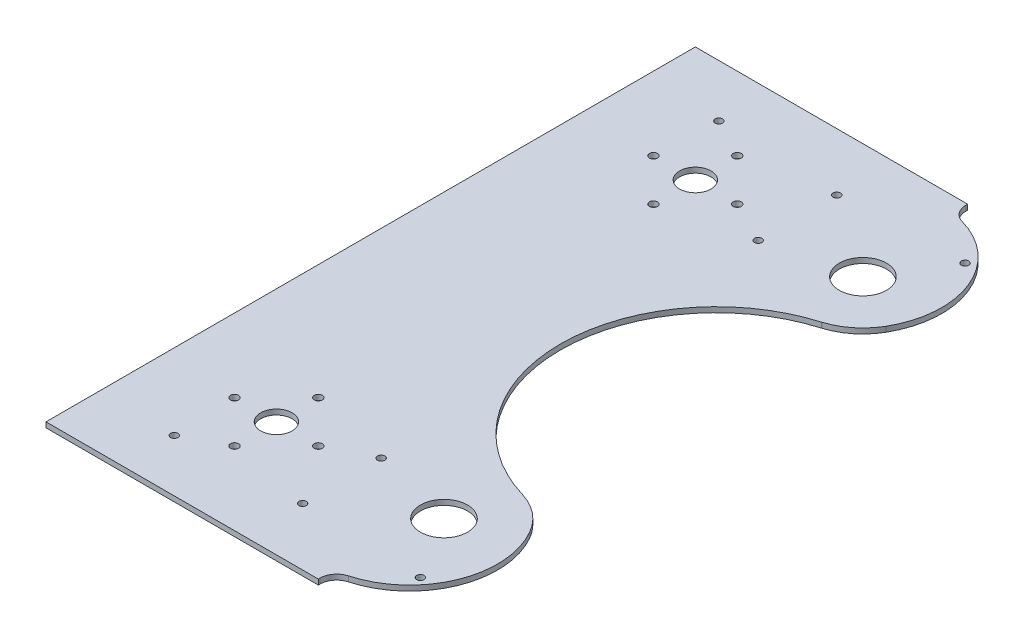
SolidWorks part; units mm, degrees
material "6061-T6 (SS)"
ref_plane "Front Plane" through (0, 0, 0) normal (0, 0, 1) x (1, 0, 0)
ref_plane "Top Plane" through (0, 0, 0) normal (0, 1, 0) x (1, 0, 0)
ref_plane "Right Plane" through (0, 0, 0) normal (1, 0, 0) x (0, 0, -1)
sketch "Sketch1" plane through (0, 0, 0) normal (0, 1, 0) x (1, 0, 0)
  line L1 (82.55, -196.85) -> (-82.55, -196.85)
  line L2 (82.55, -196.85) -> (82.55, 196.85)
  line L3 (82.55, 196.85) -> (-82.55, 196.85)
  line L4 (-82.55, -196.85) -> (-82.55, 196.85)
  line L5 (82.55, -196.85) -> (-82.55, 196.85) construction
  line L6 (82.55, 196.85) -> (-82.55, -196.85) construction
  point P0 (0, 0)
  dimension "D1" = 165.1
  dimension "D2" = 393.7
extrude "Boss-Extrude1" add sketch "Sketch1" along normal blind 3.175
sketch "Sketch3" plane through (0, 3.175, 0) normal (0, 1, 0) x (1, 0, 0)
  arc A0 (-3.175, -127) -> (-22.225, -127) centre (-12.7, -127) ccw construction
  arc A1 (-22.225, -127) -> (-3.175, -127) centre (-12.7, -127) ccw construction
  arc A2 (-3.175, -127) -> (-22.225, -127) centre (-12.7, -127) ccw
  arc A3 (-22.225, -127) -> (-3.175, -127) centre (-12.7, -127) ccw
  arc A4 (-3.175, 127) -> (-22.225, 127) centre (-12.7, 127) ccw construction
  arc A5 (-22.225, 127) -> (-3.175, 127) centre (-12.7, 127) ccw construction
  arc A6 (-3.175, 127) -> (-22.225, 127) centre (-12.7, 127) ccw
  arc A7 (-22.225, 127) -> (-3.175, 127) centre (-12.7, 127) ccw
extrude "Cut-Extrude2" cut sketch "Sketch3" against normal through all
hole_wizard "#10 (0.1935) Diameter Hole1" positions "Sketch4" profile "Sketch5" hole size "#10" standard "ANSI Inch" end condition through all
sketch "Sketch4" plane through (0, 3.175, 0) normal (0, 1, 0) x (1, 0, 0)
  arc A0 (-10.6807, -101.6) -> (-14.7193, -101.6) centre (-12.7, -101.6) ccw construction
  arc A1 (-14.7193, -101.6) -> (-10.6807, -101.6) centre (-12.7, -101.6) ccw construction
  arc A2 (-36.0807, -127) -> (-40.1193, -127) centre (-38.1, -127) ccw construction
  arc A3 (-40.1193, -127) -> (-36.0807, -127) centre (-38.1, -127) ccw construction
  arc A4 (-10.6807, -152.4) -> (-14.7193, -152.4) centre (-12.7, -152.4) ccw construction
  arc A5 (-14.7193, -152.4) -> (-10.6807, -152.4) centre (-12.7, -152.4) ccw construction
  arc A6 (14.7193, -127) -> (10.6807, -127) centre (12.7, -127) ccw construction
  arc A7 (10.6807, -127) -> (14.7193, -127) centre (12.7, -127) ccw construction
  arc A8 (-10.6807, -101.6) -> (-14.7193, -101.6) centre (-12.7, -101.6) ccw construction
  arc A9 (-14.7193, -101.6) -> (-10.6807, -101.6) centre (-12.7, -101.6) ccw construction
  arc A10 (-36.0807, -127) -> (-40.1193, -127) centre (-38.1, -127) ccw construction
  arc A11 (-40.1193, -127) -> (-36.0807, -127) centre (-38.1, -127) ccw construction
  arc A12 (-10.6807, -152.4) -> (-14.7193, -152.4) centre (-12.7, -152.4) ccw construction
  arc A13 (-14.7193, -152.4) -> (-10.6807, -152.4) centre (-12.7, -152.4) ccw construction
  arc A14 (14.7193, -127) -> (10.6807, -127) centre (12.7, -127) ccw construction
  arc A15 (10.6807, -127) -> (14.7193, -127) centre (12.7, -127) ccw construction
  arc A16 (14.7193, 127) -> (10.6807, 127) centre (12.7, 127) ccw construction
  arc A17 (10.6807, 127) -> (14.7193, 127) centre (12.7, 127) ccw construction
  arc A18 (-10.6807, 152.4) -> (-14.7193, 152.4) centre (-12.7, 152.4) ccw construction
  arc A19 (-14.7193, 152.4) -> (-10.6807, 152.4) centre (-12.7, 152.4) ccw construction
  arc A20 (-36.0807, 127) -> (-40.1193, 127) centre (-38.1, 127) ccw construction
  arc A21 (-40.1193, 127) -> (-36.0807, 127) centre (-38.1, 127) ccw construction
  arc A22 (-10.6807, 101.6) -> (-14.7193, 101.6) centre (-12.7, 101.6) ccw construction
  arc A23 (-14.7193, 101.6) -> (-10.6807, 101.6) centre (-12.7, 101.6) ccw construction
  arc A24 (14.7193, 127) -> (10.6807, 127) centre (12.7, 127) ccw
  arc A25 (10.6807, 127) -> (14.7193, 127) centre (12.7, 127) ccw
  arc A26 (-10.6807, 152.4) -> (-14.7193, 152.4) centre (-12.7, 152.4) ccw
  arc A27 (-14.7193, 152.4) -> (-10.6807, 152.4) centre (-12.7, 152.4) ccw
  arc A28 (-36.0807, 127) -> (-40.1193, 127) centre (-38.1, 127) ccw
  arc A29 (-40.1193, 127) -> (-36.0807, 127) centre (-38.1, 127) ccw
  arc A30 (-10.6807, 101.6) -> (-14.7193, 101.6) centre (-12.7, 101.6) ccw
  arc A31 (-14.7193, 101.6) -> (-10.6807, 101.6) centre (-12.7, 101.6) ccw
  point P0 (-12.7, -152.4)
  point P2 (-38.1, -127)
  point P4 (-12.7, -101.6)
  point P6 (12.7, -127)
  point P44 (-12.7, 152.4)
  point P50 (-38.1, 127)
  point P56 (-12.7, 101.6)
  point P68 (12.7, 127)
sketch "Sketch5" plane through (-12.7, 3.175, 152.4) normal (1, 0, 0) x (0, 0, 1)
  line L0 (0, 0) -> (0, 3.175)
  line L1 (0, 3.175) -> (2.4574, 3.175)
  line L2 (2.4574, 3.175) -> (2.4574, 0)
  line L5 (2.4574, 0) -> (0, 0)
  line L11 (0, -6.35) -> (0, 107.95) construction
  dimension "Thru Hole Dia." = 4.9149
  dimension "Thru Hole Depth" = 3.175
sketch "Sketch6" plane through (0, 3.175, 0) normal (0, 1, 0) x (1, 0, 0)
  line L0 (-12.7, -88.9) -> (-12.7, 88.9) construction
  line L1 (88.9, -127) -> (-12.7, -127) construction
  line L2 (88.9, 127) -> (-12.7, 127) construction
  line L3 (88.9, 127) -> (82.55, 127) construction
  line L4 (82.55, -196.85) -> (82.55, 196.85) construction
  circle A0 centre (-12.7, -127) radius 38.1 construction
  circle A1 centre (-12.7, 127) radius 38.1 construction
  circle A2 centre (88.9, -127) radius 38.1 construction
  circle A3 centre (88.9, 127) radius 38.1 construction
  dimension "D1" = 76.2
  dimension "D2" = 254
  dimension "D3" = 101.6
  dimension "D4" = 6.35
  dimension "D5" = 177.8
sketch "Sketch9" plane through (0, 0, 0) normal (0, 1, 0) x (1, 0, 0)
  line L0 (82.55, 196.85) -> (82.55, 187.5751)
  line L1 (82.55, -196.85) -> (82.55, 196.85) construction
  line L2 (82.55, 66.4249) -> (82.55, 57.15)
  line L3 (82.55, 196.85) -> (80.9625, 196.85)
  line L4 (82.55, 196.85) -> (-82.55, 196.85) construction
  line L5 (80.9625, 196.85) -> (80.9625, 57.15)
  line L6 (80.9625, 57.15) -> (82.55, 57.15)
  line L7 (0, 0) -> (145.4468, 0) construction
  line L8 (80.9625, -196.85) -> (80.9625, -57.15)
  line L9 (80.9625, -57.15) -> (82.55, -57.15)
  line L10 (82.55, -57.15) -> (82.55, -66.4249)
  line L11 (82.55, -187.5751) -> (82.55, -196.85)
  line L12 (82.55, -196.85) -> (80.9625, -196.85)
  line L13 (-82.55, -196.85) -> (82.55, -196.85) construction
  arc A0 (100.33, 90.6549) -> (121.8956, 107.95) centre (88.9, 127) ccw
  arc A1 (100.33, 90.6549) -> (82.55, 66.4249) centre (107.95, 66.4249) ccw
  arc A3 (121.8956, -107.95) -> (100.33, -90.6549) centre (88.9, -127) ccw
  arc A5 (82.55, -66.4249) -> (100.33, -90.6549) centre (107.95, -66.4249) ccw
  circle A6 centre (88.9, 127) radius 38.1 construction
  arc A8 (121.8956, -107.95) -> (82.55, -187.5751) centre (75.6667, -134.6403) cw
  arc A10 (121.8956, 107.95) -> (82.55, 187.5751) centre (75.6667, 134.6403) ccw
  point P8 (0, 0)
  point P15 (82.55, 89.4329)
  point P23 (120.6317, 105.9119)
  point P34 (0, 0)
  point P36 (0, 0)
  point P37 (0, 0)
  point P38 (121.8956, -107.9578)
  dimension "D1" = 25.4
  dimension "D4" = 139.7
  dimension "D5" = 38.1
  dimension "D2" = 25.4
  dimension "D3" = 1.5875
  dimension "D6" = 88.9
  dimension "D7" = 88.9
extrude "Boss-Extrude2" add sketch "Sketch9" along normal blind 3.175
fillet "Fillet1" radius 10.16 2 edges at (82.55, 1.5875, 187.5751) (82.55, 1.5875, -187.5751)
sketch "Sketch7" plane through (0, 3.175, 0) normal (0, 1, 0) x (1, 0, 0)
  circle A0 centre (88.9, -127) radius 14.2875
  circle A1 centre (88.9, 127) radius 14.2875
  dimension "D1" = 28.575
extrude "Cut-Extrude3" cut sketch "Sketch7" against normal through all
sketch "Sketch8" plane through (0, 3.175, 0) normal (0, 1, 0) x (1, 0, 0)
  line L0 (127, -94.4919) -> (127, 94.4919)
  arc A1 (127, 94.4919) -> (127, -94.4919) centre (127, 0) ccw
  arc A7 (121.8956, -107.95) -> (100.33, -90.6549) centre (88.9, -127) ccw construction
  arc A8 (100.33, 90.6549) -> (121.8956, 107.95) centre (88.9, 127) ccw construction
  dimension "D1" = 127
extrude "Cut-Extrude4" cut sketch "Sketch8" against normal through all
sketch "Sketch10" plane through (0, 3.175, 0) normal (0, 1, 0) x (1, 0, 0)
  circle A0 centre (38.1, -114.3) radius 2.2479 construction
  circle A1 centre (-36.5125, -165.1) radius 2.2479 construction
  circle A3 centre (38.1, -161.925) radius 2.2479 construction
  circle A4 centre (112.7125, -165.1) radius 2.2479 construction
  circle A5 centre (38.1, -114.3) radius 2.2479
  circle A6 centre (-36.5125, -165.1) radius 2.2479
  circle A8 centre (38.1, -161.925) radius 2.2479
  circle A9 centre (112.7125, -165.1) radius 2.2479
  circle A10 centre (112.7125, 165.1) radius 2.2479 construction
  circle A11 centre (38.1, 161.925) radius 2.2479 construction
  circle A13 centre (38.1, 114.3) radius 2.2479 construction
  circle A14 centre (-36.5125, 165.1) radius 2.2479 construction
  circle A15 centre (112.7125, 165.1) radius 2.2479
  circle A16 centre (38.1, 161.925) radius 2.2479
  circle A18 centre (38.1, 114.3) radius 2.2479
  circle A19 centre (-36.5125, 165.1) radius 2.2479
extrude "Cut-Extrude5" cut sketch "Sketch10" against normal through all
